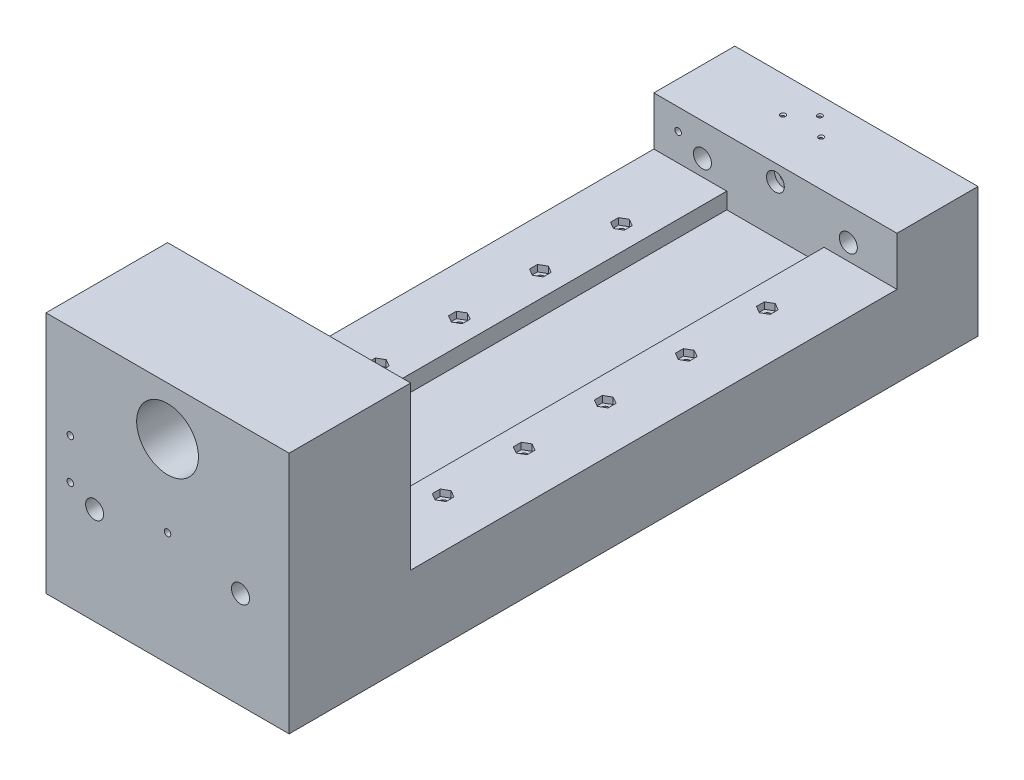
SolidWorks part; units mm, degrees
material "AISI 1020"
ref_plane "Plano frontal" through (0, 0, 0) normal (0, 0, 1) x (1, 0, 0)
ref_plane "Plano superior" through (0, 0, 0) normal (0, 1, 0) x (1, 0, 0)
ref_plane "Plano direito" through (0, 0, 0) normal (1, 0, 0) x (0, 0, -1)
sketch "Esboço1" plane through (0, 0, 0) normal (1, 0, 0) x (0, 0, -1)
  line L0 (0, 0) -> (850, 0)
  line L1 (850, 0) -> (850, 160)
  line L2 (850, 160) -> (750, 160)
  line L3 (750, 160) -> (750, 100)
  line L4 (750, 100) -> (150, 100)
  line L5 (150, 100) -> (150, 300)
  line L6 (150, 300) -> (0, 300)
  line L7 (0, 300) -> (0, 0)
  dimension "D1" = 850
  dimension "D2" = 300
  dimension "D3" = 200
  dimension "D4" = 60
  dimension "D5" = 150
  dimension "D6" = 100
extrude "Ressalto-extrusão1" add sketch "Esboço1" along normal mid plane 300
sketch "Esboço2" plane through (0, 0, 0) normal (0, 0, 1) x (1, 0, 0)
  line L0 (150, 300) -> (-150, 300) construction
  line L1 (0, 0) -> (0, 300) construction
  line L2 (-150, 300) -> (-150, 0) construction
  circle A0 centre (0, 240) radius 38.1
  circle A1 centre (0, 140) radius 4
  circle A2 centre (-90, 120) radius 11.11
  circle A3 centre (90, 120) radius 11.11
  circle A4 centre (-120, 183.7621) radius 4
  circle A5 centre (-120, 133.7621) radius 4
  dimension "D1" = 76.2
  dimension "D3" = 8
  dimension "D7" = 22.22
  dimension "D8" = 50
  dimension "D9" = 8
  dimension "D10" = 30
  dimension "D2" = 60
  dimension "D4" = 120
  dimension "D5" = 20
  dimension "D6" = 180
extrude "Corte-extrusão1" cut sketch "Esboço2" against normal up to surface (850 mm away) up to face at (0, 80, -850)
sketch "Sketch2" plane through (0, 100, 0) normal (0, 1, 0) x (1, 0, 0)
  line L0 (150, 150) -> (-150, 150) construction
  line L1 (-60, 150) -> (60, 150)
  line L2 (-60, 150) -> (-60, 750)
  line L3 (-60, 750) -> (60, 750)
  line L4 (60, 150) -> (60, 750)
  line L6 (150, 750) -> (-150, 750) construction
  point P8 (0, 150)
  point P9 (0, 150)
  dimension "D1" = 120
extrude "Cut-Extrude2" cut sketch "Sketch2" against normal blind 20
hole_wizard "CSK for M3 Flat Head Machine Screw1" positions "Sketch3" profile "Sketch5" countersink size "M3" standard "ANSI Metric"
sketch "Sketch3" plane through (0, 160, 0) normal (0, 1, 0) x (1, 0, 0)
  line L0 (-150, 850) -> (-150, 750) construction
  line L1 (150, 850) -> (-150, 850) construction
  point P0 (-46.6, 806)
  point P2 (-23.05, 828)
  point P4 (0.5, 806)
  dimension "D1" = 103.4
  dimension "D2" = 47.1
  dimension "D3" = 22
  dimension "D4" = 22
  dimension "D5" = 23.55
sketch "Sketch5" plane through (-46.6, 160, -806) normal (1, 0, 0) x (0, 0, 1)
  line L0 (0, 0) -> (0, 11.0215)
  line L1 (0, 11.0215) -> (1.7, 10)
  line L2 (1.7, 10) -> (1.7, 1.45)
  line L3 (1.7, 1.45) -> (3.15, 0)
  line L5 (3.15, 0) -> (0, 0)
  line L6 (-1.7, 1.45) -> (-3.15, 0) construction
  line L10 (0, 11.0215) -> (-1.7, 10) construction
  line L11 (0, -6.35) -> (0, 107.95) construction
  dimension "Hole Dia." = 3.4
  dimension "Hole Depth" = 10
  dimension "Near C'Sink Dia." = 6.3
  dimension "Near C'Sink Angle" = 90
  dimension "Drill Angle" = 118
sketch "Sketch6" plane through (0, 0, -750) normal (0, 0, 1) x (1, 0, 0)
  circle A0 centre (0, 140) radius 11
  dimension "D1" = 22
extrude "Cut-Extrude3" cut sketch "Sketch6" against normal blind 10
pattern_linear "LPattern1" count 2 spacing 90 along (0, 0, -1) of "Cut-Extrude3"
extrude "Cut-Extrude4" cut sketch "Sketch6<2>" along normal blind 10 from surface starting at face at (38.1, 240, -150)
sketch "Sketch6<2>" plane through (0, 0, -750) normal (0, 0, 1) x (1, 0, 0) same geometry as "Sketch6"
sketch "Sketch7" plane through (0, 100, 0) normal (0, 1, 0) x (1, 0, 0)
  line L0 (-101.11, 750) -> (-78.89, 750) construction
  line L1 (78.89, 750) -> (101.11, 750) construction
  point P0 (-90, 750)
  point P1 (90, 750)
  point P6 (-90, 650)
  point P9 (90, 650)
  point P10 (-90, 550)
  point P11 (90, 550)
  point P12 (-90, 450)
  point P13 (90, 450)
  point P14 (-90, 350)
  point P15 (90, 350)
  point P16 (-90, 250)
  point P17 (90, 250)
  dimension "D1" = 6
hole_wizard "Tap Drill for M10x1.0 Tap1" positions "Sketch8" profile "Sketch9" hole size "M10x1.0" standard "ANSI Metric"
sketch "Sketch8" plane through (0, 100, 0) normal (0, 1, 0) x (1, 0, 0)
  point P0 (-90, 650)
  point P3 (90, 650)
  point P6 (-90, 550)
  point P9 (90, 550)
  point P12 (90, 450)
  point P15 (-90, 450)
  point P18 (-90, 350)
  point P21 (-90, 250)
  point P24 (90, 250)
  point P27 (90, 350)
sketch "Sketch9" plane through (-90, 100, -650) normal (1, 0, 0) x (0, 0, 1)
  line L0 (0, 0) -> (0, 22.7039)
  line L1 (0, 22.7039) -> (4.5, 20)
  line L2 (4.5, 20) -> (4.5, 0)
  line L5 (4.5, 0) -> (0, 0)
  line L10 (0, 22.7039) -> (-4.5, 20) construction
  line L11 (0, -6.35) -> (0, 107.95) construction
  dimension "Hole Dia." = 9
  dimension "Hole Depth" = 20
  dimension "Drill Angle" = 118
sketch "Sketch10" plane through (0, 100, 0) normal (0, 1, 0) x (1, 0, 0)
  line L0 (-150, 750) -> (-150, 150) construction
  line L1 (-98.5, 645.0925) -> (-90, 640.185)
  line L2 (-90, 640.185) -> (-81.5, 645.0925)
  line L3 (-81.5, 645.0925) -> (-81.5, 654.9075)
  line L4 (-81.5, 654.9075) -> (-90, 659.815)
  line L5 (-90, 659.815) -> (-98.5, 654.9075)
  line L6 (-98.5, 654.9075) -> (-98.5, 645.0925)
  line L7 (0, -165) -> (0, 165) construction
  line L8 (98.5, 654.9075) -> (98.5, 645.0925)
  line L9 (90, 659.815) -> (98.5, 654.9075)
  line L10 (81.5, 654.9075) -> (90, 659.815)
  line L11 (81.5, 645.0925) -> (81.5, 654.9075)
  line L12 (90, 640.185) -> (81.5, 645.0925)
  line L13 (98.5, 645.0925) -> (90, 640.185)
  line L14 (-98.5, 545.0925) -> (-90, 540.185)
  line L15 (-90, 540.185) -> (-81.5, 545.0925)
  line L16 (-81.5, 545.0925) -> (-81.5, 554.9075)
  line L17 (-81.5, 554.9075) -> (-90, 559.815)
  line L18 (-90, 559.815) -> (-98.5, 554.9075)
  line L19 (-98.5, 554.9075) -> (-98.5, 545.0925)
  line L20 (98.5, 554.9075) -> (98.5, 545.0925)
  line L21 (90, 559.815) -> (98.5, 554.9075)
  line L22 (81.5, 554.9075) -> (90, 559.815)
  line L23 (81.5, 545.0925) -> (81.5, 554.9075)
  line L24 (90, 540.185) -> (81.5, 545.0925)
  line L25 (98.5, 545.0925) -> (90, 540.185)
  line L26 (-98.5, 445.0925) -> (-90, 440.185)
  line L27 (-90, 440.185) -> (-81.5, 445.0925)
  line L28 (-81.5, 445.0925) -> (-81.5, 454.9075)
  line L29 (-81.5, 454.9075) -> (-90, 459.815)
  line L30 (-90, 459.815) -> (-98.5, 454.9075)
  line L31 (-98.5, 454.9075) -> (-98.5, 445.0925)
  line L32 (98.5, 454.9075) -> (98.5, 445.0925)
  line L33 (90, 459.815) -> (98.5, 454.9075)
  line L34 (81.5, 454.9075) -> (90, 459.815)
  line L35 (81.5, 445.0925) -> (81.5, 454.9075)
  line L36 (90, 440.185) -> (81.5, 445.0925)
  line L37 (98.5, 445.0925) -> (90, 440.185)
  line L38 (-98.5, 345.0925) -> (-90, 340.185)
  line L39 (-90, 340.185) -> (-81.5, 345.0925)
  line L40 (-81.5, 345.0925) -> (-81.5, 354.9075)
  line L41 (-81.5, 354.9075) -> (-90, 359.815)
  line L42 (-90, 359.815) -> (-98.5, 354.9075)
  line L43 (-98.5, 354.9075) -> (-98.5, 345.0925)
  line L44 (98.5, 354.9075) -> (98.5, 345.0925)
  line L45 (90, 359.815) -> (98.5, 354.9075)
  line L46 (81.5, 354.9075) -> (90, 359.815)
  line L47 (81.5, 345.0925) -> (81.5, 354.9075)
  line L48 (90, 340.185) -> (81.5, 345.0925)
  line L49 (98.5, 345.0925) -> (90, 340.185)
  line L50 (-98.5, 245.0925) -> (-90, 240.185)
  line L51 (-90, 240.185) -> (-81.5, 245.0925)
  line L52 (-81.5, 245.0925) -> (-81.5, 254.9075)
  line L53 (-81.5, 254.9075) -> (-90, 259.815)
  line L54 (-90, 259.815) -> (-98.5, 254.9075)
  line L55 (-98.5, 254.9075) -> (-98.5, 245.0925)
  line L56 (98.5, 254.9075) -> (98.5, 245.0925)
  line L57 (90, 259.815) -> (98.5, 254.9075)
  line L58 (81.5, 254.9075) -> (90, 259.815)
  line L59 (81.5, 245.0925) -> (81.5, 254.9075)
  line L60 (90, 240.185) -> (81.5, 245.0925)
  line L61 (98.5, 245.0925) -> (90, 240.185)
  circle A0 centre (-90, 650) radius 8.5 construction
  circle A1 centre (90, 650) radius 8.5 construction
  circle A2 centre (-90, 550) radius 8.5 construction
  circle A3 centre (90, 550) radius 8.5 construction
  circle A4 centre (-90, 450) radius 8.5 construction
  circle A5 centre (90, 450) radius 8.5 construction
  circle A6 centre (-90, 350) radius 8.5 construction
  circle A7 centre (90, 350) radius 8.5 construction
  circle A8 centre (-90, 250) radius 8.5 construction
  circle A9 centre (90, 250) radius 8.5 construction
  dimension "D1" = 17
  dimension "D2" = 5
extrude "Cut-Extrude5" cut sketch "Sketch10" against normal blind 8
